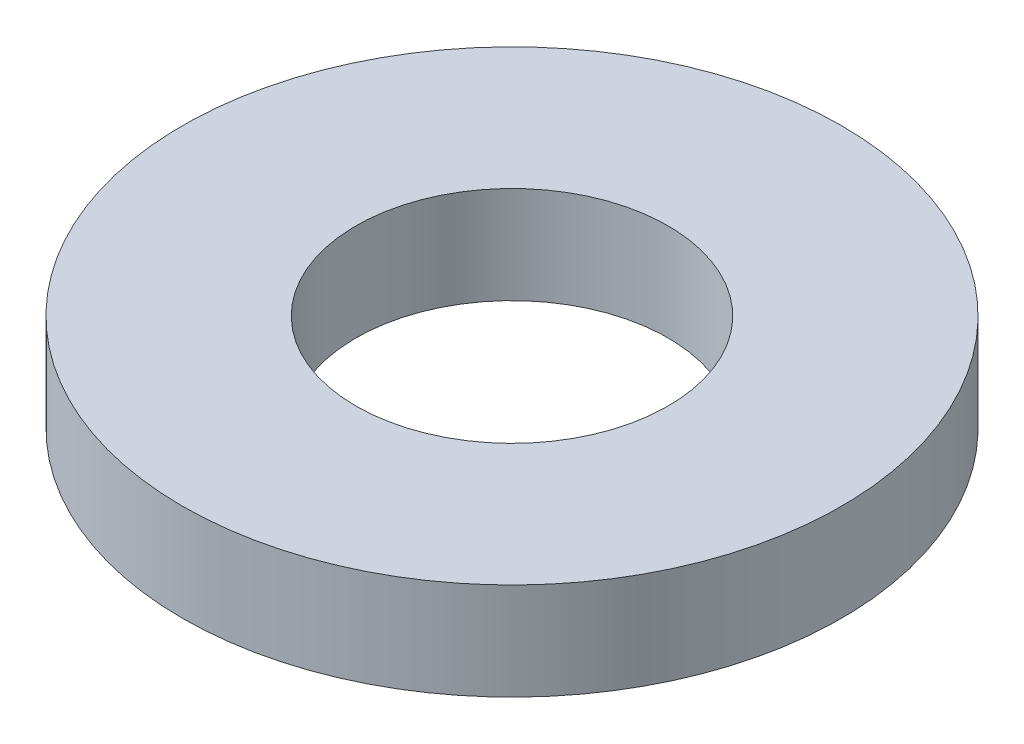
SolidWorks part; units mm, degrees
ref_plane "Front Plane" through (0, 0, 0) normal (0, 0, 1) x (1, 0, 0)
ref_plane "Top Plane" through (0, 0, 0) normal (0, 1, 0) x (1, 0, 0)
ref_plane "Right Plane" through (0, 0, 0) normal (1, 0, 0) x (0, 0, -1)
sketch "Sketch1" plane through (0, 0, 0) normal (0, 1, 0) x (1, 0, 0)
  circle A0 centre (0, 0) radius 47.5
  dimension "FLANGE_OD" = 95
extrude "Boss-Extrude1" add sketch "Sketch1" along normal blind 14
sketch "Sketch2" plane through (0, 0, 0) normal (0, 1, 0) x (1, 0, 0)
  circle A0 centre (0, 0) radius 22.5
  dimension "BORE_D" = 45
extrude "Cut-Extrude1" cut sketch "Sketch2" along normal through all
sketch "Sketch3" plane through (0, 14, 0) normal (0, 1, 0) x (1, 0, 0)
  circle A0 centre (0, 0) radius 17.7568 construction
  circle A1 centre (-17.7568, 0) radius 2.4585
  dimension "BOLT_D" = 4.917
  dimension "BOLT_PCD" = 35.5135
extrude "Cut-Extrude2" cut sketch "Sketch3" against normal blind 11.9051 rebuild error yes
pattern_circular "CirPattern1" count 8 over 360 rebuild error yes
